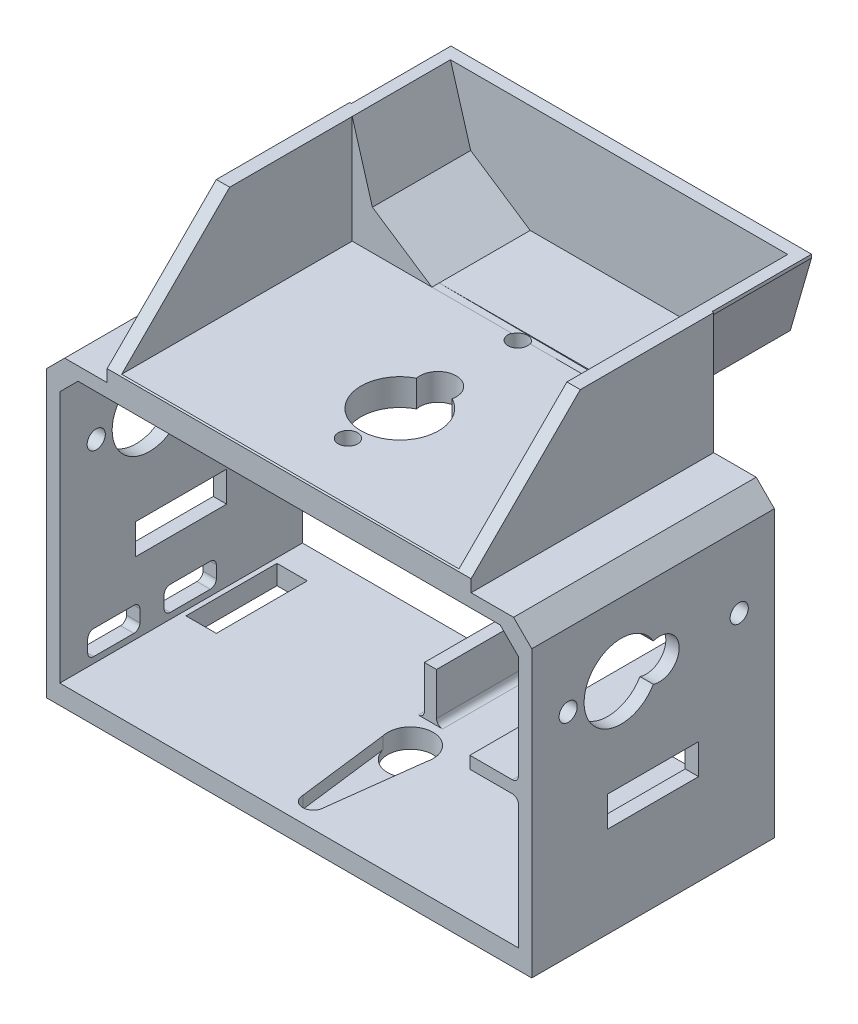
SolidWorks part; units mm, degrees
ref_plane "Front Plane" through (0, 0, 0) normal (0, 0, 1) x (1, 0, 0)
ref_plane "Top Plane" through (0, 0, 0) normal (0, 1, 0) x (1, 0, 0)
ref_plane "Right Plane" through (0, 0, 0) normal (1, 0, 0) x (0, 0, -1)
sketch "Sketch1" plane through (0, 0, 0) normal (0, 0, 1) x (1, 0, 0)
  line L0 (-37.8, -27.8) -> (-37.8, 27.8)
  line L1 (-40, -30) -> (40, -30)
  line L2 (-40, -30) -> (-40, 30)
  line L3 (-40, 30) -> (40, 30)
  line L4 (40, -30) -> (40, 30)
  line L5 (-40, -30) -> (40, 30) construction
  line L6 (-40, 30) -> (40, -30) construction
  line L7 (-30, 30) -> (30, 30)
  line L8 (-30, 30) -> (-30, 50)
  line L9 (-30, 50) -> (-27.8, 50)
  line L10 (30, 30) -> (30, 50)
  line L11 (-37.8, 27.8) -> (37.8, 27.8)
  line L12 (37.8, -27.8) -> (37.8, 27.8)
  line L13 (-37.8, -27.8) -> (37.8, -27.8)
  line L15 (27.8, 32.2) -> (27.8, 47.8)
  line L16 (-27.8, 32.2) -> (27.8, 32.2)
  line L17 (-27.8, 32.2) -> (-27.8, 47.8)
  line L18 (27.8, 47.8) -> (27.8, 50)
  line L19 (-27.8, 47.8) -> (-27.8, 50)
  line L20 (27.8, 50) -> (30, 50)
  line L22 (-30, 50) -> (30, 50) construction
  line L23 (-27.8, 47.8) -> (27.8, 47.8) construction
  point P0 (0, 0)
  dimension "D1" = 80
  dimension "D2" = 60
  dimension "D3" = 10
  dimension "D4" = 10
  dimension "D5" = 20
  dimension "D6" = 2.2
  dimension "D7" = 2.2
extrude "Boss-Extrude1" add sketch "Sketch1" along normal blind 40
chamfer "Chamfer1" distance 18 angle 45 2 edges at (28.9, 50, 40) (-28.9, 50, 40)
sketch "Sketch2" plane through (0, 0, 0) normal (0, 0, -1) x (-1, 0, 0)
  line L1 (-30, 50) -> (30, 50)
  line L2 (-30, 50) -> (-30, 30)
  line L3 (-30, 30) -> (30, 30)
  line L4 (30, 50) -> (30, 30)
extrude "Boss-Extrude2" add sketch "Sketch2" against normal blind 1.8
sketch "Sketch3" plane through (37.8, 0, 0) normal (-1, 0, 0) x (0, 0, 1)
  line L0 (0, -27.8) -> (0, 27.8) construction
  line L1 (40, -30) -> (40, 30) construction
  line L2 (40, -30) -> (0, -30) construction
  circle A0 centre (34, 15) radius 1.5
  circle A1 centre (5.8, 15) radius 1.5
  dimension "D1" = 3
  dimension "D2" = 3
  dimension "D3" = 5.8
  dimension "D4" = 6
  dimension "D5" = 45
sketch "Sketch4" plane through (40, 0, 0) normal (1, 0, 0) x (0, 0, -1)
  line L0 (0, -30) -> (0, 30) construction
  line L1 (-40, -30) -> (0, -30) construction
  circle A0 centre (-25.25, 15) radius 6.125
  circle A1 centre (-18.95, 15) radius 3.25
  dimension "D1" = 12.25
  dimension "D2" = 6.5
  dimension "D3" = 18.95
  dimension "D4" = 25.25
  dimension "D5" = 45
sketch "Sketch5" plane through (0, 0, 40) normal (0, 0, 1) x (1, 0, 0)
  line L0 (40, -30) -> (40, 30) construction
  line L1 (-40, 30) -> (40, 30)
  line L2 (-40, 30) -> (-40, -20)
  line L3 (-40, -20) -> (40, -20)
  line L4 (40, 30) -> (40, -20)
  line L5 (-37.8, 27.8) -> (-37.8, -17.8)
  line L6 (-37.8, -17.8) -> (37.8, -17.8)
  line L7 (37.8, 27.8) -> (37.8, -17.8)
  line L8 (-37.8, 27.8) -> (37.8, 27.8)
  dimension "D1" = 50
  dimension "D2" = 2.2
extrude "Boss-Extrude3" add sketch "Sketch5" against normal blind 40
sketch "Sketch6" plane through (0, 0, 40) normal (0, 0, 1) x (1, 0, 0)
  line L0 (-40, -30) -> (-40, 30) construction
  line L1 (-40, -20) -> (40, -20)
  line L2 (-40, -20) -> (-40, -30)
  line L3 (-40, -30) -> (40, -30)
  line L4 (40, -20) -> (40, -30)
  line L5 (-37.8, -20) -> (37.8, -20) construction
extrude "Cut-Extrude3" cut sketch "Sketch6" against normal blind 40
sketch "Sketch7" plane through (0, 27.8, 0) normal (0, -1, 0) x (1, 0, 0)
  line L0 (37.8, 40) -> (37.8, 0) construction
  line L1 (-37.8, 0) -> (37.8, 0) construction
  circle A0 centre (0, 21.75) radius 6.4
  circle A1 centre (0, 15.45) radius 3
  circle A4 centre (0, 30.3) radius 1.6
  circle A5 centre (0, 2.3) radius 1.6
  dimension "D2" = 3.2
  dimension "D3" = 12.8
  dimension "D4" = 6
  dimension "D9" = 3.2
  dimension "D5" = 37.8
  dimension "D6" = 37.8
  dimension "D7" = 15.45
  dimension "D8" = 21.75
  dimension "D10" = 8.55
  dimension "D11" = 19.45
extrude "Cut-Extrude4" cut sketch "Sketch7" against normal blind 40 contours A5 | A0 A1 | A0 A1 | A1 A0 | A4
extrude "Cut-Extrude5" cut sketch "Sketch3" along normal through all and the other way blind 40
extrude "Cut-Extrude6" cut sketch "Sketch4" against normal through all contours A1 A0 | A0 A1 | A0 A1
sketch "Sketch10" plane through (0, -17.8, 0) normal (0, 1, 0) x (1, 0, 0)
  line L1 (-40, 0) -> (40, 0)
  line L2 (-40, 0) -> (-40, -40)
  line L3 (-40, -40) -> (40, -40)
  line L4 (40, 0) -> (40, -40)
extrude "Boss-Extrude4" add sketch "Sketch10" along normal blind 1
sketch "Sketch12" plane through (-40, 0, 0) normal (-1, 0, 0) x (0, 0, 1)
  line L0 (0, -20) -> (40, -20) construction
  line L1 (12.5, 0) -> (27.5, 0)
  line L2 (12.5, 0) -> (12.5, -5)
  line L3 (12.5, -5) -> (27.5, -5)
  line L4 (27.5, 0) -> (27.5, -5)
  point P8 (20, -20)
  point P9 (20, -5)
  dimension "D1" = 15
  dimension "D2" = 5
extrude "Cut-Extrude10" cut sketch "Sketch12" against normal through all
sketch "Sketch13" plane through (0, -20, 0) normal (0, -1, 0) x (1, 0, 0)
  line L0 (-40, 0) -> (40, 0) construction
  line L1 (-37, 20) -> (-32, 20)
  line L2 (-37, 20) -> (-37, 5)
  line L3 (-37, 5) -> (-32, 5)
  line L4 (-32, 20) -> (-32, 5)
  line L5 (32, 20) -> (37, 20)
  line L6 (32, 20) -> (32, 5)
  line L7 (32, 5) -> (37, 5)
  line L8 (37, 20) -> (37, 5)
  line L9 (40, 0) -> (40, 40) construction
  line L10 (-40, 0) -> (-40, 40) construction
  dimension "D1" = 5
  dimension "D2" = 5
  dimension "D3" = 15
  dimension "D4" = 15
  dimension "D5" = 5
  dimension "D6" = 5
  dimension "D7" = 3
  dimension "D8" = 3
extrude "Cut-Extrude11" cut sketch "Sketch13" against normal blind 10
sketch "Sketch14" plane through (0, 0, 1.8) normal (0, 0, 1) x (1, 0, 0)
  line L0 (-27.8, 50) -> (-24.4693, 38.7087)
  line L1 (-24.4693, 38.7087) -> (-14.6599, 32.2)
  line L2 (-1.5199, 32.2) -> (-27.8, 32.2) construction
  line L3 (-14.6599, 32.2) -> (14.6599, 32)
  line L4 (30, 32) -> (-30, 32) construction
  line L5 (14.6599, 32) -> (24.5057, 38.6087)
  line L6 (24.5057, 38.6087) -> (27.8, 50)
  line L7 (27.8, 50) -> (-27.8, 50)
  point P2 (0, 32.1)
  dimension "D1" = 140
  dimension "D2" = 140
extrude "Cut-Extrude12" cut sketch "Sketch14" against normal through all
sketch "Sketch15" plane through (0, 0, 1.8) normal (0, 0, 1) x (1, 0, 0)
  line L1 (27.8, 50) -> (24.5057, 38.6087) construction
  line L2 (24.5057, 38.6087) -> (14.9579, 32.2) construction
  line L5 (-14.6599, 32.2) -> (-24.4693, 38.7087) construction
  line L6 (-24.4693, 38.7087) -> (-27.8, 50) construction
  line L9 (27.8, 50) -> (24.5057, 38.6087)
  line L10 (24.5057, 38.6087) -> (14.9579, 32.2)
  line L13 (-14.6599, 32.2) -> (-24.4693, 38.7087)
  line L14 (-24.4693, 38.7087) -> (-27.8, 50)
  line L16 (-15.7657, 30.5335) -> (-26.1816, 37.4447)
  line L17 (-26.1816, 37.4447) -> (-29.7183, 49.4341)
  line L18 (29.7213, 49.4444) -> (26.2247, 37.3538)
  line L19 (26.2247, 37.3538) -> (16.0725, 30.5394)
  line L20 (-29.7183, 49.4341) -> (-29.7183, 50)
  line L21 (-30, 50) -> (-27.8, 50) construction
  line L22 (-29.7183, 50) -> (-27.8, 50)
  line L23 (-15.7657, 30.5335) -> (16.0725, 30.5394)
  line L24 (-14.6599, 32.2) -> (14.9579, 32.2)
  line L25 (29.7213, 49.4444) -> (29.7213, 50)
  line L26 (27.8, 50) -> (30, 50) construction
  line L27 (29.7213, 50) -> (27.8, 50)
  dimension "D1" = 2
extrude "Boss-Extrude5" add sketch "Sketch15" against normal blind 15 from offset 1.2 offset against normal yes
sketch "Sketch22" plane through (0, 0, -14.4) normal (0, 0, -1) x (-1, 0, 0)
  line L0 (-27.8, 50) -> (27.8, 50)
  line L14 (-16.0725, 30.5394) -> (15.7657, 30.5335)
  line L15 (15.7657, 30.5335) -> (26.1816, 37.4447)
  line L16 (26.1816, 37.4447) -> (29.7183, 49.4341)
  line L17 (29.7183, 49.4341) -> (29.7183, 50)
  line L18 (29.7183, 50) -> (27.8, 50)
  line L19 (27.8, 50) -> (24.4693, 38.7087)
  line L20 (24.4693, 38.7087) -> (14.6599, 32.2)
  line L21 (14.6599, 32.2) -> (-14.9579, 32.2)
  line L22 (-14.9579, 32.2) -> (-24.5057, 38.6087)
  line L23 (-24.5057, 38.6087) -> (-27.8, 50)
  line L24 (-27.8, 50) -> (-29.7213, 50)
  line L25 (-29.7213, 50) -> (-29.7213, 49.4444)
  line L26 (-29.7213, 49.4444) -> (-26.2247, 37.3538)
  line L27 (-26.2247, 37.3538) -> (-16.0725, 30.5394)
  line L28 (-16.0725, 30.5394) -> (15.7657, 30.5335)
  line L29 (15.7657, 30.5335) -> (26.1816, 37.4447)
  line L30 (26.1816, 37.4447) -> (29.7183, 49.4341)
  line L31 (29.7183, 49.4341) -> (29.7183, 50)
  line L32 (29.7183, 50) -> (27.8, 50)
  line L33 (27.8, 50) -> (24.4693, 38.7087)
  line L34 (24.4693, 38.7087) -> (14.6599, 32.2)
  line L35 (14.6599, 32.2) -> (-14.9579, 32.2)
  line L36 (-14.9579, 32.2) -> (-24.5057, 38.6087)
  line L37 (-24.5057, 38.6087) -> (-27.8, 50)
  line L38 (-27.8, 50) -> (-29.7213, 50)
  line L39 (-29.7213, 50) -> (-29.7213, 49.4444)
  line L40 (-29.7213, 49.4444) -> (-26.2247, 37.3538)
  line L41 (-26.2247, 37.3538) -> (-16.0725, 30.5394)
  line M15 (-16.0725, 30.5394) -> (15.7657, 30.5335)
  line M16 (15.7657, 30.5335) -> (26.1816, 37.4447)
  line M17 (26.1816, 37.4447) -> (29.7183, 49.4341)
  line M18 (29.7183, 49.4341) -> (29.7183, 50)
  line M19 (29.7183, 50) -> (27.8, 50)
  line M20 (27.8, 50) -> (24.4693, 38.7087)
  line M21 (24.4693, 38.7087) -> (14.6599, 32.2)
  line M22 (14.6599, 32.2) -> (-14.9579, 32.2)
  line M23 (-14.9579, 32.2) -> (-24.5057, 38.6087)
  line M24 (-24.5057, 38.6087) -> (-27.8, 50)
  line M25 (-27.8, 50) -> (-29.7213, 50)
  line M26 (-29.7213, 50) -> (-29.7213, 49.4444)
  line M27 (-29.7213, 49.4444) -> (-26.2247, 37.3538)
  line M28 (-26.2247, 37.3538) -> (-16.0725, 30.5394)
  dimension "D1" = 0
extrude "Boss-Extrude8" add sketch "Sketch22" along normal blind 2 contours M28 M15 M16 M17 M18 M19 M20 M21 M22 M23 M24 M25 M26 M27 | L0 M24 M23 M22 M21 M20
chamfer "Chamfer2" distance 3 angle 45 2 edges at (37.8, 27.8, 20) (-37.8, 27.8, 20)
chamfer "Chamfer3" distance 3 angle 45 2 edges at (40, 30, 20) (-40, 30, 20)
sketch "Sketch25" plane through (0, -20, 0) normal (0, -1, 0) x (1, 0, 0)
  line L0 (-40, 0) -> (-40, 40) construction
  line L1 (-3.6346, 20.9231) -> (-1.75, 36)
  line L2 (1.75, 36) -> (3.6346, 20.9231)
  line L3 (-37, 20) -> (-37, 5) construction
  arc A0 (-3.6346, 20.9231) -> (3.6346, 20.9231) centre (0, 20) ccw
  arc A1 (1.75, 36) -> (-1.75, 36) centre (0, 36) ccw
  point P5 (-40, 20)
  dimension "D1" = 7.5
  dimension "D2" = 3.5
  dimension "D3" = 16
  dimension "D4" = 33.3654
  dimension "D5" = 40.6346
extrude "Cut-Extrude15" cut sketch "Sketch25" against normal blind 2.2 from offset 1.2 offset against normal yes
sketch "Sketch26" plane through (0, -18.8, 0) normal (0, 1, 0) x (1, 0, 0)
  circle A0 centre (0, -20) radius 3.75
extrude "Cut-Extrude16" cut sketch "Sketch26" against normal blind 2.2
sketch "Sketch27" plane through (0, 0, 40) normal (0, 0, 1) x (1, 0, 0)
  line L0 (-37.8, -16.8) -> (37.8, -16.8) construction
  line L1 (-0.7, -16.8) -> (-2.7, -16.8)
  line L2 (-0.7, -16.8) -> (-0.7, -8.8)
  line L3 (-0.7, -8.8) -> (-2.7, -8.8)
  line L4 (-2.7, -16.8) -> (-2.7, -8.8)
  line L5 (-0.7, -16.8) -> (-2.7, -8.8) construction
  line L6 (-0.7, -8.8) -> (-2.7, -16.8) construction
  line L7 (37.8, -16.8) -> (37.8, 24.8) construction
  point P4 (-1.7, -12.8)
  dimension "D1" = 2
  dimension "D2" = 38.5
  dimension "D3" = 8
extrude "Boss-Extrude9" add sketch "Sketch27" against normal up to surface (15 mm away) from offset 25 up to face at (0.0198, 31.5972, 0) offset against normal yes
fillet "Fillet1" radius 1 2 edges at (-2.7, -16.8, 7.5) (-0.7, -16.8, 7.5)
sketch "Sketch28" plane through (0, 0, 40) normal (0, 0, 1) x (1, 0, 0)
  line L0 (37.8, -16.8) -> (37.8, 24.8) construction
  line L1 (37.8, 4.7) -> (29.8, 4.7)
  line L2 (37.8, 4.7) -> (37.8, 6.7)
  line L3 (37.8, 6.7) -> (29.8, 6.7)
  line L4 (29.8, 4.7) -> (29.8, 6.7)
  line L5 (37.8, 4.7) -> (29.8, 6.7) construction
  line L6 (37.8, 6.7) -> (29.8, 4.7) construction
  line L7 (-37.8, -16.8) -> (37.8, -16.8) construction
  point P4 (33.8, 5.7)
  dimension "D1" = 21.5
  dimension "D2" = 8
  dimension "D3" = 2
extrude "Boss-Extrude10" add sketch "Sketch28" against normal up to surface (40 mm away) up to face at (0.0198, 31.5972, 0)
fillet "Fillet2" radius 1 2 edges at (37.8, 4.7, 20) (37.8, 6.7, 20)
sketch "Sketch29" plane through (-37.8, 0, 0) normal (1, 0, 0) x (0, 0, -1)
  line L0 (-40, -16.8) -> (-40, 24.8) construction
  line L1 (-34.4, -11.8) -> (-27.8, -11.8)
  line L2 (-35.4, -12.8) -> (-35.4, -14.8)
  line L3 (-34.4, -15.8) -> (-27.8, -15.8)
  line L4 (-26.8, -12.8) -> (-26.8, -14.8)
  line L5 (-35.4, -11.8) -> (-26.8, -15.8) construction
  line L6 (-35.4, -15.8) -> (-26.8, -11.8) construction
  line L7 (-21.8, -11.8) -> (-15.2, -11.8)
  line L8 (-22.8, -12.8) -> (-22.8, -14.8)
  line L9 (-21.8, -15.8) -> (-15.2, -15.8)
  line L10 (-14.2, -12.8) -> (-14.2, -14.8)
  line L11 (-22.8, -11.8) -> (-14.2, -15.8) construction
  line L12 (-22.8, -15.8) -> (-14.2, -11.8) construction
  line L13 (-40, -16.8) -> (0, -16.8) construction
  arc A0 (-15.2, -15.8) -> (-14.2, -14.8) centre (-15.2, -14.8) ccw
  arc A1 (-15.2, -11.8) -> (-14.2, -12.8) centre (-15.2, -12.8) cw
  arc A2 (-21.8, -11.8) -> (-22.8, -12.8) centre (-21.8, -12.8) ccw
  arc A3 (-22.8, -14.8) -> (-21.8, -15.8) centre (-21.8, -14.8) ccw
  arc A4 (-35.4, -14.8) -> (-34.4, -15.8) centre (-34.4, -14.8) ccw
  arc A5 (-27.8, -15.8) -> (-26.8, -14.8) centre (-27.8, -14.8) ccw
  arc A6 (-27.8, -11.8) -> (-26.8, -12.8) centre (-27.8, -12.8) cw
  arc A7 (-34.4, -11.8) -> (-35.4, -12.8) centre (-34.4, -12.8) ccw
  point P4 (-31.1, -13.8)
  point P9 (-18.5, -13.8)
  dimension "D8" = 1
  dimension "D1" = 8.6
  dimension "D2" = 4.6
  dimension "D3" = 4
  dimension "D4" = 1
  dimension "D5" = 4
  dimension "D6" = 8.6
  dimension "D7" = 4
extrude "Cut-Extrude17" cut sketch "Sketch29" against normal through all
